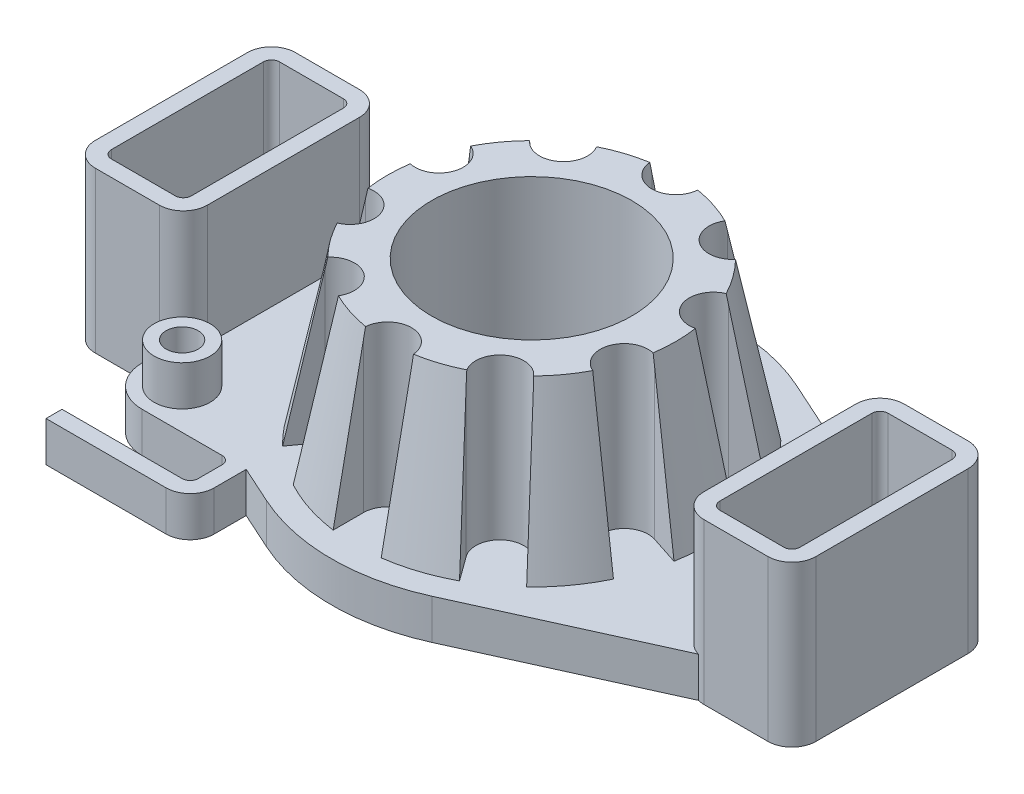
SolidWorks part; units mm, degrees
material "Nickel"
ref_plane "Front Plane" through (0, 0, 0) normal (0, 0, 1) x (1, 0, 0)
ref_plane "Top Plane" through (0, 0, 0) normal (0, 1, 0) x (1, 0, 0)
ref_plane "Right Plane" through (0, 0, 0) normal (1, 0, 0) x (0, 0, -1)
sketch "Sketch1" plane through (0, 0, 0) normal (0, 1, 0) x (1, 0, 0)
  line L0 (0, 0) -> (-56.3349, 0) construction
  line L1 (-45, 12.5) -> (-33, 12.5)
  line L2 (-45, 12.5) -> (-45, -12.5)
  line L3 (-45, -12.5) -> (-33, -12.5)
  line L4 (-33, 12.5) -> (-33, -12.5)
  line L5 (-33, 12.5) -> (-10.313, 22.7737)
  line L6 (-33, -12.5) -> (-10.313, -22.7737)
  line L7 (0, 0) -> (0, 34.2271) construction
  line L8 (33, 12.5) -> (10.313, 22.7737)
  line L9 (33, -12.5) -> (10.313, -22.7737)
  line L10 (45, -12.5) -> (33, -12.5)
  line L11 (33, 12.5) -> (33, -12.5)
  line L12 (45, 12.5) -> (45, -12.5)
  line L13 (45, 12.5) -> (33, 12.5)
  circle A0 centre (0, 0) radius 25
  circle A1 centre (0, 0) radius 12.5
  dimension "D1" = 50
  dimension "D5" = 25
  dimension "D2" = 25
  dimension "D3" = 12
  dimension "D4" = 45
extrude "Boss-Extrude1" add sketch "Sketch1" along normal blind 5 contours A0 A1 | A0 L9 L11 L8 | L12 L13 L11 L10 | A0 L5 L4 L6 | L4 L1 L2 L3 region at (-39, 0, 0) region at (-26.87, 0, 0) region at (0, 0, -24.2929) region at (26.87, 0, 0) region at (39, 0, 0)
sketch "Sketch2" plane through (0, 0, 0) normal (0, 0, 1) x (1, 0, 0)
  line L0 (0, 0) -> (0, 33.8556) construction
  line L1 (12.5, 5) -> (12.5, 25)
  line L2 (12.5, 25) -> (18, 25)
  line L3 (18, 25) -> (22, 5)
  line L4 (33, 5) -> (10.313, 5) construction
  line L5 (22, 5) -> (12.5, 5)
  line L6 (33, 0) -> (10.313, 0) construction
  dimension "D1" = 25
  dimension "D2" = 18
  dimension "D3" = 22
revolve "Revolve1" add sketch "Sketch2" angle 360 about L0
sketch "Sketch3" plane through (0, 25, 0) normal (0, 1, 0) x (1, 0, 0)
  line L1 (0, 0) -> (0, 34.2271) construction
  line L4 (-3, 18) -> (-3, 22)
  line L5 (-3, 22) -> (3, 22)
  line L6 (3, 18) -> (3, 22)
  circle A0 centre (0, 18) radius 3
  circle A1 centre (0, 0) radius 18 construction
  circle A2 centre (0, 0) radius 22 construction
  circle M3 centre (0, 0) radius 18
  dimension "D1" = 6
extrude "Cut-Extrude1" cut sketch "Sketch3" against normal up to surface (20 mm away) contours A0 M3 | A0 M3 | A0 L6 L5 L4 region at (0, 25, -21.0417) region at (0, 25, -19.2272) region at (0, 25, -16.6828) up to face at (0, 5, -22)
pattern_circular "CirPattern1" count 10 over 360 about axis through (0, 25, 0) along (0, -1, 0) of "Cut-Extrude1"
sketch "Sketch4" plane through (0, 5, 0) normal (0, 1, 0) x (1, 0, 0)
  line L10 (-33, 10.5) -> (-33, -10.5)
  line L11 (33, 10.5) -> (33, -10.5)
  line L12 (-31, 12.5) -> (-45, 12.5)
  line L13 (-45, 12.5) -> (-45, -12.5)
  line L14 (-45, -12.5) -> (-31, -12.5)
  line L15 (-31, 12.5) -> (-31, -12.5)
  line L16 (45, 12.5) -> (31, 12.5)
  line L17 (31, 12.5) -> (31, -12.5)
  line L18 (31, -12.5) -> (45, -12.5)
  line L19 (45, -12.5) -> (45, 12.5)
  line L20 (9.4879, -20.9518) -> (32.5683, -10.5)
  line L21 (32.5683, -10.5) -> (43, -10.5)
  line L22 (43, -10.5) -> (43, 10.5)
  line L23 (43, 10.5) -> (32.5683, 10.5)
  line L24 (32.5683, 10.5) -> (9.4879, 20.9518)
  line L25 (-9.4879, 20.9518) -> (-32.5683, 10.5)
  line L26 (-32.5683, 10.5) -> (-43, 10.5)
  line L27 (-43, 10.5) -> (-43, -10.5)
  line L28 (-43, -10.5) -> (-32.5683, -10.5)
  line L29 (-32.5683, -10.5) -> (-9.4879, -20.9518)
  line L31 (33, -10.5) -> (43, -10.5)
  line L32 (43, -10.5) -> (43, 10.5)
  line L33 (43, 10.5) -> (33, 10.5)
  line L36 (-33, 10.5) -> (-43, 10.5)
  line L37 (-43, 10.5) -> (-43, -10.5)
  line L38 (-43, -10.5) -> (-33, -10.5)
  arc A4 (-9.4879, -20.9518) -> (9.4879, -20.9518) centre (0, 0) ccw
  arc A5 (9.4879, 20.9518) -> (-9.4879, 20.9518) centre (0, 0) ccw
  dimension "D2" = 10
  dimension "D3" = 10
  dimension "D1" = 2
  dimension "D4" = 2
extrude "Boss-Extrude2" add sketch "Sketch4" along normal blind 15
extrude "Cut-Extrude4" cut sketch "Sketch4<3>" against normal through all contours L37 L38 L10 L36 | L32 L33 L11 L31 region at (-38, 5, 0) region at (38, 5, 0)
sketch "Sketch4<3>" plane through (0, 5, 0) normal (0, 1, 0) x (1, 0, 0) same geometry as "Sketch4"
sketch "Sketch5" plane through (0, 0, 0) normal (0, 1, 0) x (1, 0, 0)
  line L0 (-33, -12.5) -> (-10.313, -22.7737) construction
  line L2 (-33, -12.5) -> (-33, -20.6512)
  line L3 (-33, -20.6512) -> (-17, -20.6512)
  line L5 (-15, -20.6512) -> (-33, -12.5)
  line L7 (-33, -20.6512) -> (-17, -20.6512)
  line L8 (-33, -25.6512) -> (-33, -27.6512)
  line L9 (-33, -27.6512) -> (-15, -27.6512)
  line L10 (-15, -20.6512) -> (-15, -27.6512)
  line L11 (-33, -20.6512) -> (-17, -20.6512)
  line L13 (-33, -25.6512) -> (-17, -25.6512)
  line L14 (-17, -20.6512) -> (-17, -25.6512)
  dimension "D1" = 18
  dimension "D2" = 7
  dimension "D3" = 2
  dimension "D4" = 2
extrude "Boss-Extrude3" add sketch "Sketch5" along normal blind 5 contours L3 L14 L13 L8 L9 L10 L5 L2 region at (-24.0971, 0, 16.7899)
fillet "Fillet1" radius 3 9 edges at (45, 10, -12.5) (45, 10, 12.5) (-45, 10, -12.5) (-45, 10, 12.5) (-15, 2.5, 27.6512) (31, 12.5, 12.5) (31, 12.5, -12.5) (-31, 12.5, -12.5) (-31, 12.5, 12.5)
fillet "Fillet2" radius 1 10 edges at (-17, 2.5, 20.6512) (-17, 2.5, 25.6512) (-43, 10, 10.5) (-43, 10, -10.5) (43, 10, 10.5) (43, 10, -10.5) (33, 10, 10.5) (33, 10, -10.5) (-33, 10, 10.5) (-33, 10, -10.5)
fillet "Fillet3" radius 5 1 edges at (-33, 2.5, 20.6512)
sketch "Sketch6" plane through (0, 0, 0) normal (0, 1, 0) x (1, 0, 0)
  circle A0 centre (-28, -15.6512) radius 3.5
  circle A1 centre (-28, -15.6512) radius 2
  dimension "D1" = 7
  dimension "D2" = 4
extrude "Boss-Extrude4" add sketch "Sketch6" along normal blind 10
extrude "Cut-Extrude3" cut sketch "Sketch6<2>" against normal through all and the other way through all contours A1
sketch "Sketch6<2>" plane through (0, 0, 0) normal (0, 1, 0) x (1, 0, 0) same geometry as "Sketch6"
